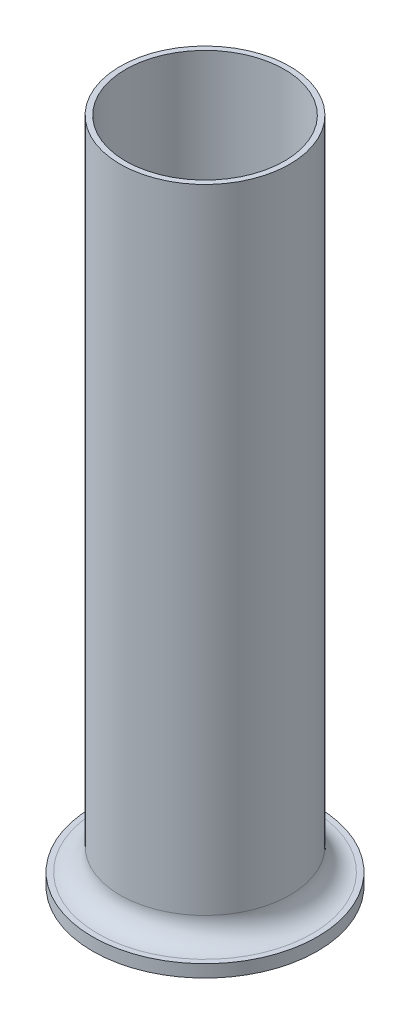
SolidWorks part; units mm, degrees
ref_plane "정면" through (0, 0, 0) normal (0, 0, 1) x (1, 0, 0)
ref_plane "윗면" through (0, 0, 0) normal (0, 1, 0) x (1, 0, 0)
ref_plane "우측면" through (0, 0, 0) normal (1, 0, 0) x (0, 0, -1)
sketch "스케치1" plane through (0, 0, 0) normal (0, 1, 0) x (1, 0, 0)
  circle A0 centre (0, 0) radius 25.25
  dimension "D1" = 50.5
extrude "보스-돌출1" add sketch "스케치1" along normal blind 2.8
sketch "스케치2" plane through (0, 2.8, 0) normal (0, 1, 0) x (1, 0, 0)
  circle A0 centre (0, 0) radius 19.05
  dimension "D1" = 38.1
extrude "보스-돌출2" add sketch "스케치2" along normal blind 147.2
fillet "필렛1" radius 5 1 edges at (0, 2.8, 19.05)
sketch "스케치3" plane through (0, 150, 0) normal (0, 1, 0) x (1, 0, 0)
  circle A0 centre (0, 0) radius 17.85
  dimension "D1" = 35.7
extrude "컷-돌출1" cut sketch "스케치3" against normal through all
sketch "스케치4" plane through (0, 0, 0) normal (0, -1, 0) x (1, 0, 0)
  circle A0 centre (0, 0) radius 21.75
  dimension "D1" = 43.5
sketch "스케치5" plane through (0, 0, 0) normal (0, 0, 1) x (1, 0, 0)
  line L0 (-21.75, 0) -> (21.75, 0) construction
  circle A0 centre (-21.75, 0) radius 1.8
  dimension "D2" = 3.6
  dimension "D1" = 21.75
sweep "컷-스윕1" cut profiles "스케치5" path "스케치4"
